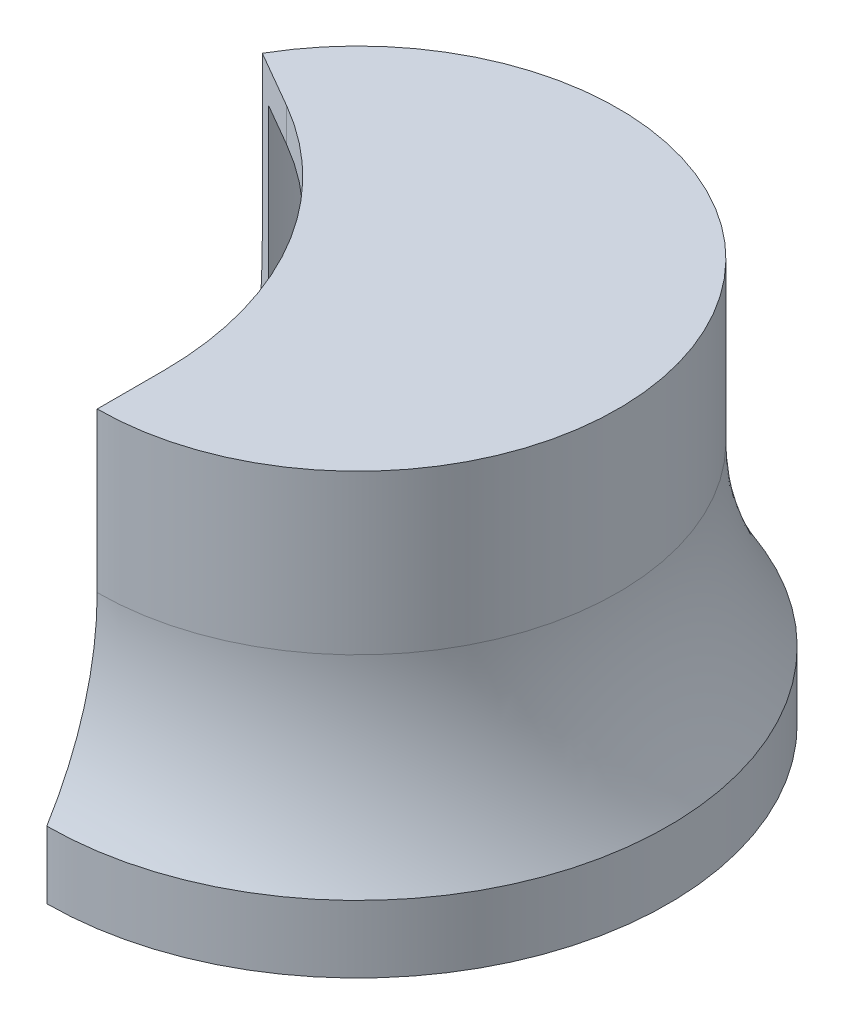
SolidWorks part; units mm, degrees
ref_plane "Front Plane" through (0, 0, 0) normal (0, 0, 1) x (1, 0, 0)
ref_plane "Top Plane" through (0, 0, 0) normal (0, 1, 0) x (1, 0, 0)
ref_plane "Right Plane" through (0, 0, 0) normal (1, 0, 0) x (0, 0, -1)
sketch "Sketch1" plane through (0, 0, 0) normal (0, 1, 0) x (1, 0, 0)
  circle A0 centre (0, 0) radius 14.5
  circle A1 centre (0, 0) radius 17
  circle A2 centre (0, 0) radius 18.5
  circle A3 centre (0, 0) radius 15.5
  dimension "D1" = 29
  dimension "D2" = 34
  dimension "D3" = 37
  dimension "D4" = 31
extrude "Boss-Extrude2" add sketch "Sketch1" along normal blind 2 contours A0 | A2
extrude "Boss-Extrude3" add sketch "Sketch1<4>" against normal blind 2 contours A2 A1 region at (-17.9767, 0, 0)
sketch "Sketch1<4>" plane through (0, 0, 0) normal (0, 1, 0) x (1, 0, 0) same geometry as "Sketch1"
extrude "Boss-Extrude4" add sketch "Sketch1<5>" along normal blind 20 contours A3 A0 region at (-15.0616, 0, 0)
sketch "Sketch1<5>" plane through (0, 0, 0) normal (0, 1, 0) x (1, 0, 0) same geometry as "Sketch1"
extrude "Boss-Extrude5" add sketch "Sketch1<6>" along normal blind 2 from surface contours A3 starting at face at (0, 20, 14.5)
sketch "Sketch1<6>" plane through (0, 0, 0) normal (0, 1, 0) x (1, 0, 0) same geometry as "Sketch1"
sketch "Sketch2" plane through (0, 0, 0) normal (0, 1, 0) x (1, 0, 0)
  line L0 (0, 0) -> (-20, 11.547)
  line L1 (0, 0) -> (-20, 0)
  line L2 (0, 0) -> (0, -20)
  line L3 (0, -20) -> (-20, -20)
  line L4 (-20, 0) -> (-20, -20)
  line L5 (-20, 11.547) -> (-20, 0)
  dimension "D1" = 20
  dimension "D2" = 20
  dimension "D3" = 120
extrude "Cut-Extrude3" cut sketch "Sketch2" against normal mid plane 62 contours L1 L4 L3 L2 | L0 L5 L1 region at (-13.3333, 0, -3.849) region at (-10, 0, 10)
fillet "Fillet2" radius 20 1 edges at (0, 21, 0)
fillet "Fillet3" radius 20 1 edges at (13.4234, 2, -7.75)
